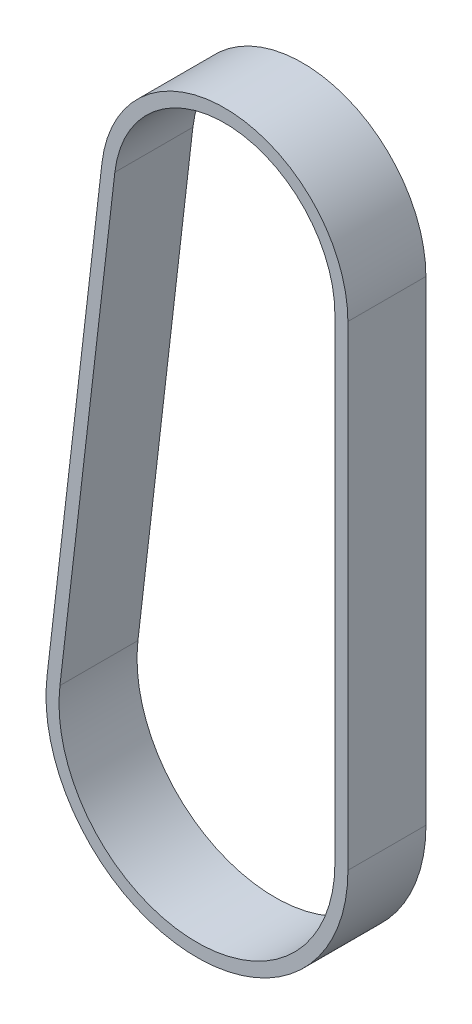
SolidWorks part; units mm, degrees
ref_plane "Front Plane" through (0, 0, 0) normal (0, 0, 1) x (1, 0, 0)
ref_plane "Top Plane" through (0, 0, 0) normal (0, 1, 0) x (1, 0, 0)
ref_plane "Right Plane" through (0, 0, 0) normal (1, 0, 0) x (0, 0, -1)
sketch "Sketch2" plane through (0, 0, 0) normal (0, 0, 1) x (1, 0, 0)
  line L0 (0, 0) -> (1, 0) construction
  line L1 (0, 0) -> (0, 1) construction
  line L2 (15.9074, 54.8177) -> (15.9155, 0.0024)
  line L3 (-15.8088, 1.8399) -> (-9.472, 56.2877)
  arc A0 (-9.472, 56.2877) -> (15.9074, 54.8177) centre (3.175, 54.8158) cw
  arc A1 (15.9155, 0.0024) -> (-15.8088, 1.8399) centre (0, 0) cw
extrude "Extrude-Thin1" add sketch "Sketch2" along normal blind 9 thin thin type one direction wall 1.5
